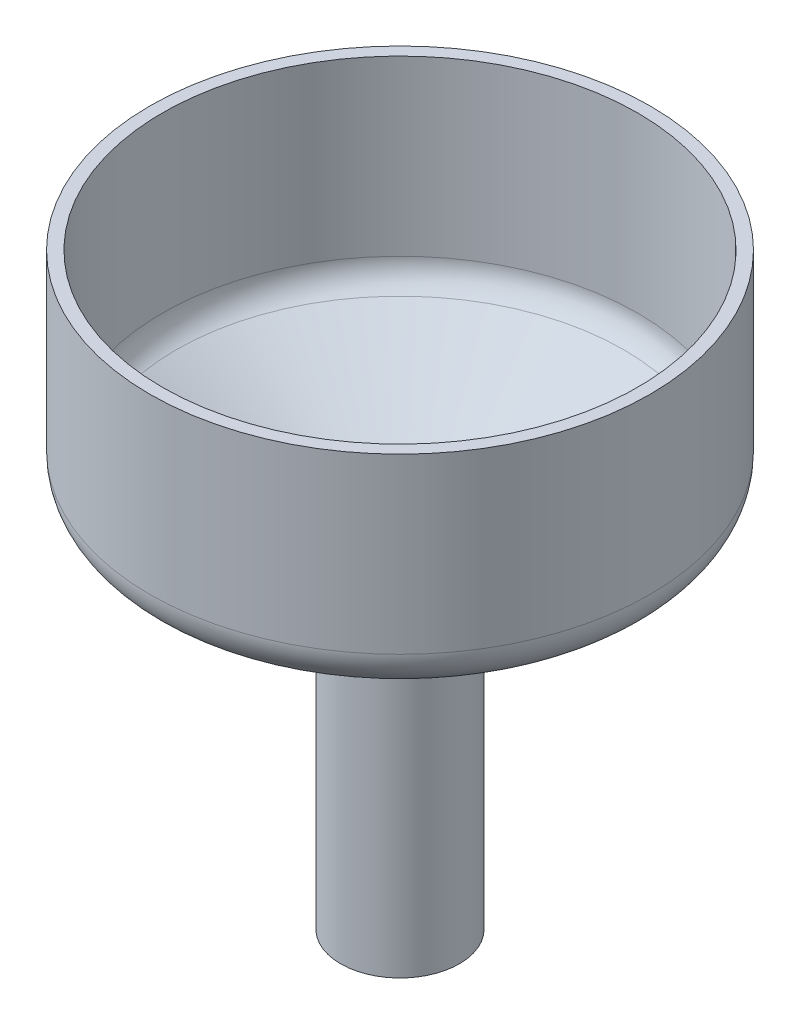
SolidWorks part; units mm, degrees
ref_plane "Front Plane" through (0, 0, 0) normal (0, 0, 1) x (1, 0, 0)
ref_plane "Top Plane" through (0, 0, 0) normal (0, 1, 0) x (1, 0, 0)
ref_plane "Right Plane" through (0, 0, 0) normal (1, 0, 0) x (0, 0, -1)
sketch "Croquis1" plane through (0, 0, 0) normal (0, 1, 0) x (1, 0, 0)
  circle A0 centre (0, 0) radius 7.25
  dimension "D1" = 14.5
extrude "Saliente-Extruir1" add sketch "Croquis1" along normal blind 34
ref_plane "Plano1" through (0, 47.8, 0) normal (0, 1, 0) x (1, 0, 0)
sketch "Croquis2" plane through (0, 47.8, 0) normal (0, 1, 0) x (1, 0, 0)
  circle A0 centre (0, 0) radius 30.5
  dimension "D1" = 61
extrude "Saliente-Extruir2" add sketch "Croquis2" along normal blind 24 separate body
sketch "Croquis3" plane through (0, 34, 0) normal (0, 1, 0) x (1, 0, 0)
  circle A0 centre (0, 0) radius 7.25
loft "Recubrir1" add profiles "Croquis3", "Croquis2<2>" connector at (-4.5188, 34, -5.6695) connector at (-22.1868, 47.8, -20.9283)
sketch "Croquis2<2>" plane through (0, 47.8, 0) normal (0, 1, 0) x (1, 0, 0) same geometry as "Croquis2"
fillet "Redondeo1" radius 5 1 edges at (0, 47.8, 30.5)
shell "Vaciado1" thickness 1.5 removed face at (0, 0, 7.25) removed face at (0, 71.8, 30.5)
